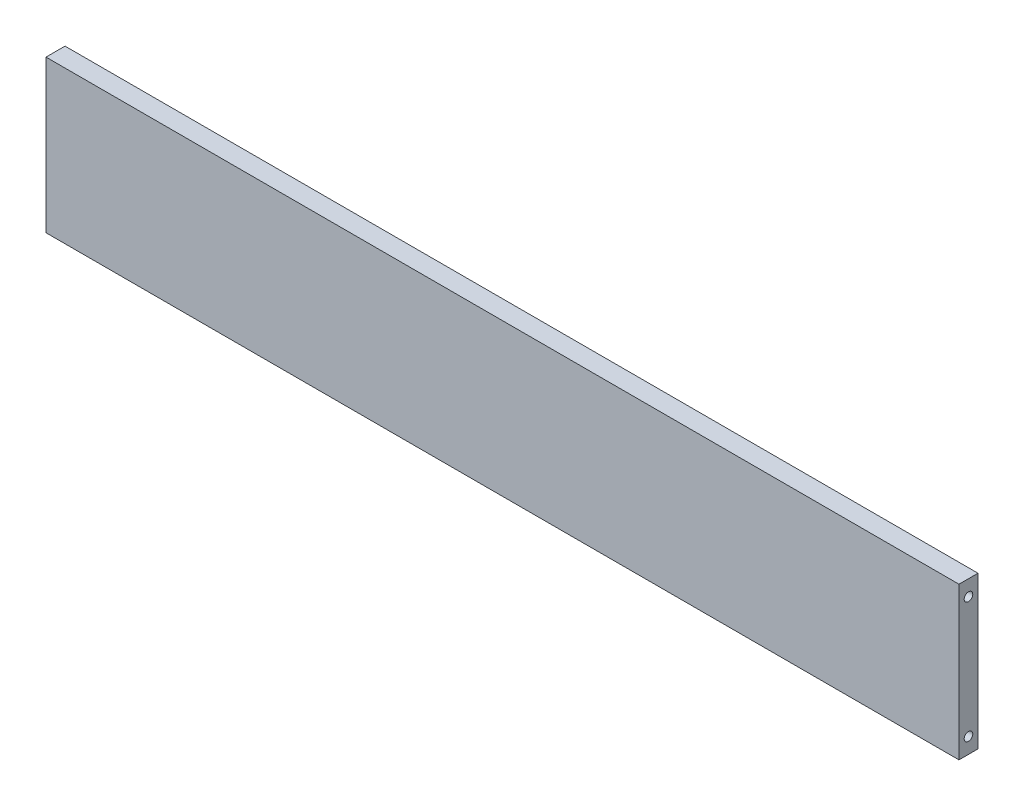
SolidWorks part; units mm, degrees
ref_plane "Front Plane" through (0, 0, 0) normal (0, 0, 1) x (1, 0, 0)
ref_plane "Top Plane" through (0, 0, 0) normal (0, 1, 0) x (1, 0, 0)
ref_plane "Right Plane" through (0, 0, 0) normal (1, 0, 0) x (0, 0, -1)
sketch "Sketch1" plane through (0, 0, 0) normal (0, 0, 1) x (1, 0, 0)
  line L1 (192, 32) -> (-192, 32)
  line L2 (192, 32) -> (192, -32)
  line L3 (192, -32) -> (-192, -32)
  line L4 (-192, 32) -> (-192, -32)
  line L5 (192, 32) -> (-192, -32) construction
  line L6 (192, -32) -> (-192, 32) construction
  point P0 (0, 0)
  dimension "D1" = 384
  dimension "D2" = 64
extrude "Boss-Extrude1" add sketch "Sketch1" along normal blind 8
sketch "Sketch2" plane through (-192, 0, 0) normal (-1, 0, 0) x (0, 0, 1)
  line L0 (0, 0) -> (8, 0) construction
  line L1 (8, 32) -> (8, -32) construction
  line L2 (4, 32) -> (4, -32) construction
  line L3 (8, 32) -> (0, 32) construction
  line L4 (8, -32) -> (0, -32) construction
  circle A0 centre (4, 25.445) radius 1.8
  circle A1 centre (4, -25.445) radius 1.8
  dimension "D1" = 25.445
extrude "Cut-Extrude1" cut sketch "Sketch2" against normal up to next
